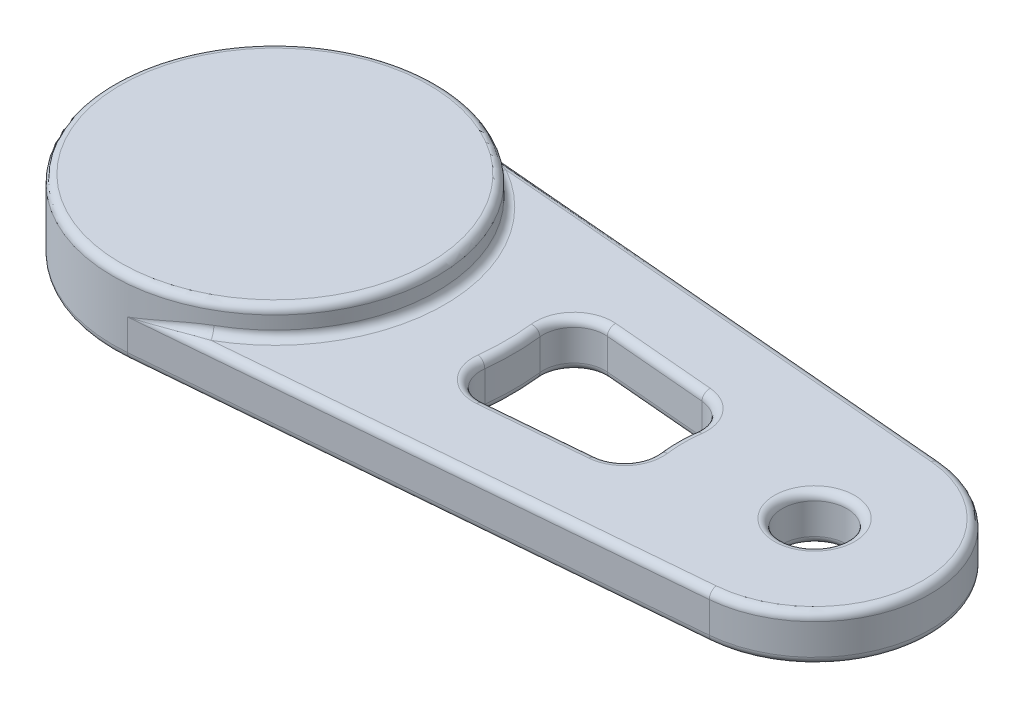
SolidWorks part; units mm, degrees
ref_plane "Front Plane" through (0, 0, 0) normal (0, 0, 1) x (1, 0, 0)
ref_plane "Top Plane" through (0, 0, 0) normal (0, 1, 0) x (1, 0, 0)
ref_plane "Right Plane" through (0, 0, 0) normal (1, 0, 0) x (0, 0, -1)
sketch "Sketch1" plane through (0, 0, 0) normal (0, 1, 0) x (1, 0, 0)
  line L0 (0.9, 10.4614) -> (35.6429, 7.4724)
  line L1 (0.9, -10.4614) -> (35.6429, -7.4724)
  arc A0 (0.9, 10.4614) -> (0.9, -10.4614) centre (0, 0) ccw
  circle A1 centre (35, 0) radius 2.1
  arc A2 (35.6429, -7.4724) -> (35.6429, 7.4724) centre (35, 0) ccw
  dimension "D1" = 21
  dimension "D2" = 4.2
  dimension "D3" = 15
  dimension "D4" = 35
extrude "Boss-Extrude1" add sketch "Sketch1" along normal blind 3
sketch "Sketch2" plane through (0, 3, 0) normal (0, 1, 0) x (1, 0, 0)
  circle A0 centre (0, 0) radius 10.5
extrude "Boss-Extrude2" add sketch "Sketch2" along normal blind 1.85 contours A0
sketch "Sketch3" plane through (0, 3, 0) normal (0, 1, 0) x (1, 0, 0)
  line L6 (14.9095, -4.2376) -> (35.2143, -2.4908)
  line L7 (35.2143, 2.4908) -> (14.9095, 4.2376)
  line L8 (17.5548, -4.0101) -> (24.2661, -3.4327)
  line L9 (24.2661, 3.4327) -> (17.5548, 4.0101)
  arc A4 (26.0775, 1.1782) -> (26.0775, -1.1782) centre (35, 0) ccw
  arc A5 (26.0775, -1.1782) -> (24.2661, -3.4327) centre (24.0947, -1.44) cw
  arc A6 (14.9095, -4.2376) -> (14.9095, 4.2376) centre (0, 0) ccw
  arc A7 (35.2143, -2.4908) -> (35.2143, 2.4908) centre (35, 0) ccw
  arc A8 (15.3967, -1.7869) -> (15.3967, 1.7869) centre (0, 0) ccw
  arc A9 (26.0775, 1.1782) -> (24.2661, 3.4327) centre (24.0947, 1.44) ccw
  arc A10 (15.3967, -1.7869) -> (17.5548, -4.0101) centre (17.3833, -2.0174) ccw
  arc A11 (15.3967, 1.7869) -> (17.5548, 4.0101) centre (17.3833, 2.0174) cw
  dimension "D2" = 18
  dimension "D3" = 2
  dimension "D1" = 5
extrude "Cut-Extrude1" cut sketch "Sketch3" against normal blind 5
fillet "Fillet1" radius 0.5 27 edges at (18.2714, 3, 8.9669) (42.5, 3, 0) (42.5, 0, 0) (18.2714, 0, 8.9669) (15.5, 0, 0) (15.9483, 0, -3.4105) (20.9104, 0, -3.7214) (25.6538, 0, -2.6927) (26, 0, 0) (25.6538, 0, 2.6927) (20.9104, 0, 3.7214) (15.5, 3, 0) (15.9483, 3, -3.4105) (20.9104, 3, -3.7214) (25.6538, 3, -2.6927) (26, 3, 0) (25.6538, 3, 2.6927) (20.9104, 3, 3.7214) (35, 0, 2.1) (35, 3, 2.1) (0, 4.85, 10.5) (10.5, 3, 0) (-10.5, 0, 0) (18.2714, 3, -8.9669) (18.2714, 0, -8.9669) (15.9483, 0, 3.4105) (15.9483, 3, 3.4105)
